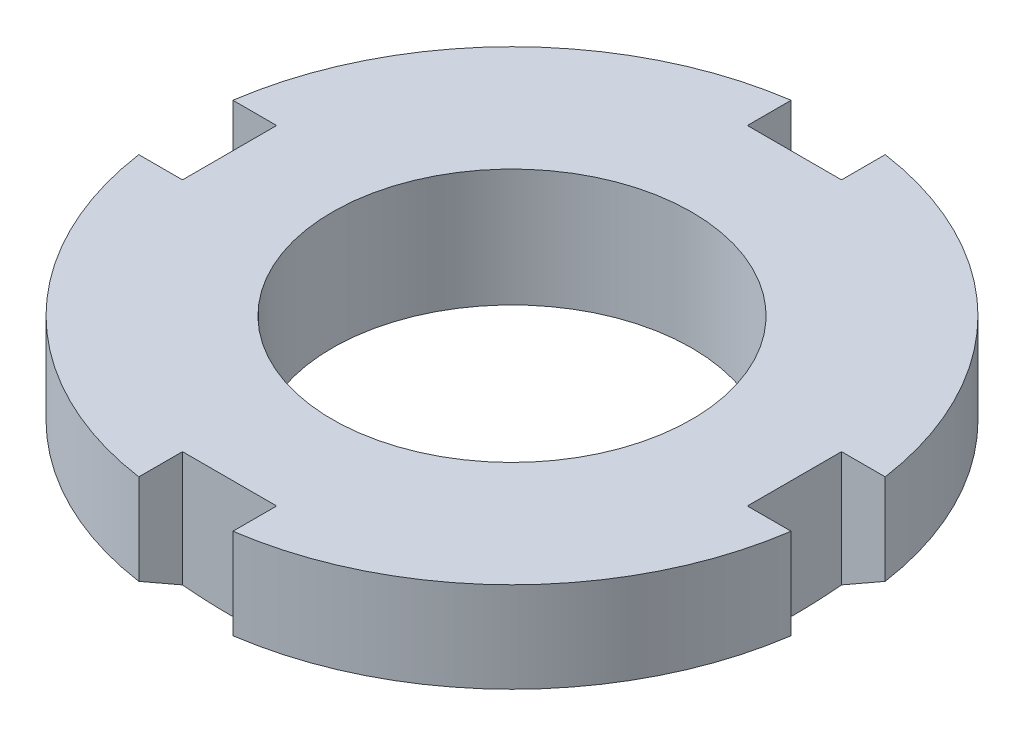
SolidWorks part; units mm, degrees
revolve "Base" add sketch "Esquisse1" angle 360 about L2
sketch "Esquisse1" plane through (0, 0, 0) normal (0, 0, 1) x (1, 0, 0)
  line L1 (7.634, 5) -> (14, 5)
  line L2 (0, 0) -> (0, 1.3) construction
  line L3 (14, 5) -> (14, 1.1547)
  line L4 (12, 0) -> (14, 1.1547)
  line L5 (12, 0) -> (7.634, 0)
  line L6 (-8.5, 0) -> (8.5, 0) construction
  line L7 (7.634, 0) -> (7.634, 5)
  line L8 (-14, 0) -> (14, 0) construction
  dimension "Hauteur" = 5
  dimension "D4" = 30
  dimension "D3" = 12
  dimension "Diamètre nominal" = 17
  dimension "Diamètre extérieur" = 28
  dimension "D6" = 7.634
  dimension "D1" = 14
ref_plane "Face" through (0, 0, 0) normal (0, 0, 1) x (1, 0, 0)
ref_plane "Dessus" through (0, 0, 0) normal (0, 1, 0) x (1, 0, 0)
ref_plane "Droite" through (0, 0, 0) normal (1, 0, 0) x (0, 0, -1)
ref_axis "Axe1" through (0, 5.25, 0) along (0, -1, 0)
sketch "Esquisse2" plane through (0, 5, -4) normal (0, -1, 0) x (1, 0, 0)
  line L0 (0, -10) -> (0, 18) construction
  line L1 (14, 4) -> (-14, 4) construction
  line L2 (2, -10) -> (-2, -10)
  line L3 (2, -10) -> (2, -8)
  line L4 (2, -8) -> (-2, -8)
  line L5 (-2, -10) -> (-2, -8)
  line L6 (-2, 18) -> (-2, 16)
  line L7 (2, 16) -> (-2, 16)
  line L8 (2, 18) -> (2, 16)
  line L9 (2, 18) -> (-2, 18)
  line L10 (12, 6) -> (12, 2)
  line L11 (-14, 6) -> (-12, 6)
  line L12 (-14, 6) -> (-14, 2)
  line L13 (-14, 2) -> (-12, 2)
  line L14 (-12, 6) -> (-12, 2)
  line L15 (14, 2) -> (12, 2)
  line L16 (14, 6) -> (14, 2)
  line L17 (14, 6) -> (12, 6)
  circle A0 centre (0, 4) radius 14 construction
  dimension "D1" = 2
  dimension "D2" = 4
  dimension "D3" = 2
extrude "Encoches" cut sketch "Esquisse2" along normal through all
ref_plane "Plan filet" through (0, -1, 0) normal (0, 1, 0) x (-1, 0, 0)
sketch "Esquisse3" plane through (0, -1, -0.75) normal (0, 1, 0) x (1, 0, 0)
  circle A0 centre (0, -0.75) radius 10
  dimension "Diamètre nominal" = 20
sketch "Esquisse4" plane through (0, 0, 0) normal (0, 0, 1) x (1, 0, 0)
  line L0 (8.5, -1) -> (7.6209, -0.5027)
  line L1 (7.6209, -0.5027) -> (7.6209, -0.75)
  line L3 (8.5, -1) -> (7.1209, -1) construction
  line L4 (7.1209, -0.75) -> (7.1209, -1.25)
  line L5 (7.6209, -0.75) -> (7.1209, -0.75)
  line L6 (8.5, -1) -> (7.6209, -1.4973)
  line L7 (0, 0) -> (0, 3.4973) construction
  line L8 (9.3178, -1) -> (-9.3178, -1) construction
  line L9 (7.6209, -1.4973) -> (7.6209, -1.25)
  line L10 (7.6209, -1.25) -> (7.1209, -1.25)
  line L11 (7.6296, -0.5076) -> (7.6296, -1) construction
  line L12 (0, 0) -> (0, 1.3) construction
  dimension "Pas" = 1
  dimension "D1" = 1.01
  dimension "D5" = 0.5
  dimension "D3" = 8.5
  dimension "D2" = 29.5
curve "Hélice1" pitch 1 height 7 turns 7 parameters "Pas"=1
sweep "Filetage" [suppressed] cut profiles "Esquisse4" path "Hélice1"
equation "\"D1@Esquisse1\" = \"Diamètre extérieur@Esquisse1\"/2"
equation "\"D6@Esquisse1\" = \"Diamètre nominal@Esquisse1\"/2-(\"Pas@Hélice1\"*sqr(3)/2)"
equation "\"D1@Esquisse2\" = \"Largeur fente@Esquisse2\"/2"
equation "\"D2@Esquisse2\" = \"Largeur fente@Esquisse2\""
equation "\"D3@Esquisse2\" = \"D2@Esquisse2\"/2"
equation "\"D3@Esquisse1\" = \"D1@Esquisse1\"-\"D3@Esquisse2\""
equation "\"D3@Hélice1\" = \"Hauteur@Esquisse1\"+(\"Pas@Hélice1\"*2)"
equation "\"D5@Hélice1\" = \"D3@Hélice1\"/\"Pas@Hélice1\""
equation "\"D1@Plan filet\" = \"Pas@Hélice1\""
equation "\"D5@Esquisse4\" = \"Pas@Esquisse4\"/2"
equation "\"D4@Esquisse4\" = \"Pas@Esquisse4\"/2"
equation "\"D1@Esquisse4\" = \"Pas@Esquisse4\"+(\"Pas@Esquisse4\"/100)"
equation "\"D3@Esquisse4\" = \"Diamètre nominal@Esquisse1\"/2"
